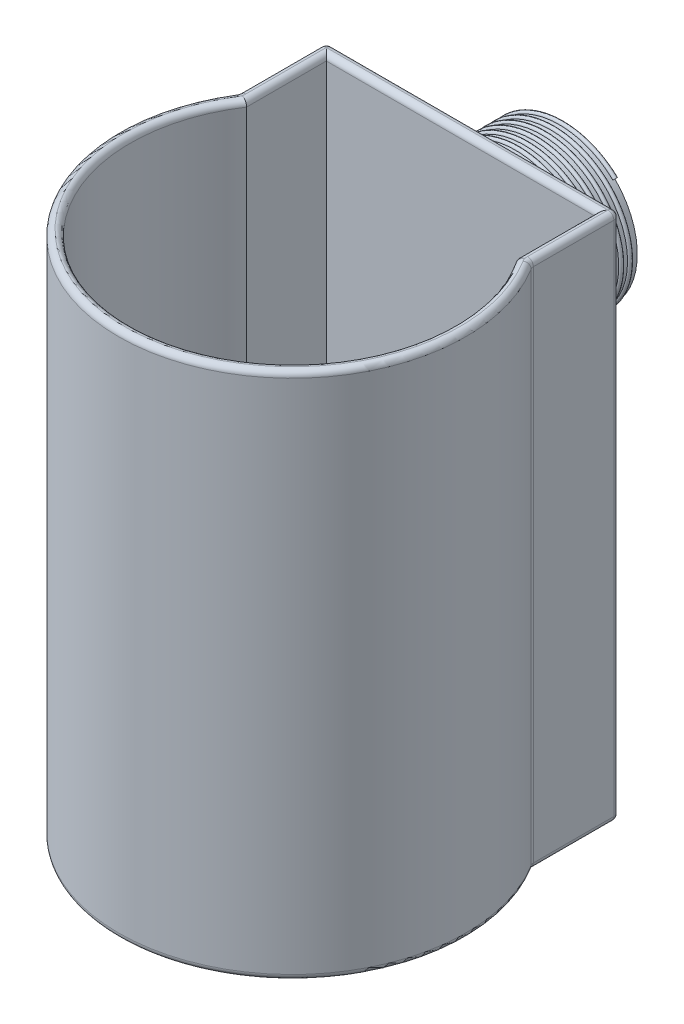
SolidWorks part; units mm, degrees
ref_plane "Front Plane" through (0, 0, 0) normal (0, 0, 1) x (1, 0, 0)
ref_plane "Top Plane" through (0, 0, 0) normal (0, 1, 0) x (1, 0, 0)
ref_plane "Right Plane" through (0, 0, 0) normal (1, 0, 0) x (0, 0, -1)
sketch "Sketch1" plane through (0, 0, 0) normal (0, 0, 1) x (1, 0, 0)
  circle A0 centre (0, 0) radius 1.3
  dimension "D1" = 2.6
extrude "Boss-Extrude1" add sketch "Sketch1" against normal blind 1.5
sketch "Sketch2" plane through (0, 0, 0) normal (0, 1, 0) x (1, 0, 0)
  line L0 (0, 0) -> (-2.5, 0)
  line L1 (-2.5, 0) -> (-2.5, -1.5)
  line L3 (2.5, -1.5) -> (2.5, 0)
  line L4 (2.5, 0) -> (0, 0)
  arc A1 (-2.5, -1.5) -> (2.5, -1.5) centre (0, -3.0816) ccw
  dimension "D1" = 2.5
  dimension "D2" = 2.5
  dimension "D3" = 1.5
extrude "Boss-Extrude2" add sketch "Sketch2" along normal blind 2 and the other way blind 7
sketch "Sketch3" plane through (0, 2, 0) normal (0, 1, 0) x (1, 0, 0)
  line L9 (2.3, -0.2) -> (-2.3, -0.2)
  line L10 (-2.3, -0.2) -> (-2.3, -1.5591)
  line L11 (2.3, -1.5591) -> (2.3, -0.2)
  line L12 (2.3, -0.2) -> (-2.3, -0.2)
  line L13 (-2.3, -0.2) -> (-2.3, -1.5591)
  line L14 (2.3, -1.5591) -> (2.3, -0.2)
  arc A1 (-2.3, -1.5591) -> (2.3, -1.5591) centre (0, -3.0816) ccw
  arc A2 (-2.3, -1.5591) -> (2.3, -1.5591) centre (0, -3.0816) ccw
  dimension "D1" = 0.2
extrude "Cut-Extrude1" cut sketch "Sketch3" against normal blind 8.5
fillet "Fillet1" radius 0.1 17 edges at (-2.5, -7, 0.75) (2.5, -7, 0.75) (-2.5, 2, 0.75) (2.5, 2, 0.75) (-2.3, 2, 0.8795) (2.3, 2, 0.8795) (0, -7, 0) (-2.5, -2.5, 0) (2.5, -2.5, 0) (0, 2, 0) (0, 2, 0.2) (0, 2, 5.8399) (0, 2, 6.0399) (2.3, -2.25, 1.5591) (0, -7, 6.0399) (-2.5, -2.5, 1.5) (2.5, -2.5, 1.5)
sketch "Sketch4" plane through (0, 0, -1.5) normal (0, 0, -1) x (-1, 0, 0)
  circle A1 centre (0, 0) radius 1.3
  circle A2 centre (0, 0) radius 1.3
  dimension "D1" = 0
curve "Helix/Spiral1" pitch 0.15 height 1.5 turns 10
sweep "Sweep1" add path "Helix/Spiral1" parameters "D3"=0.07
